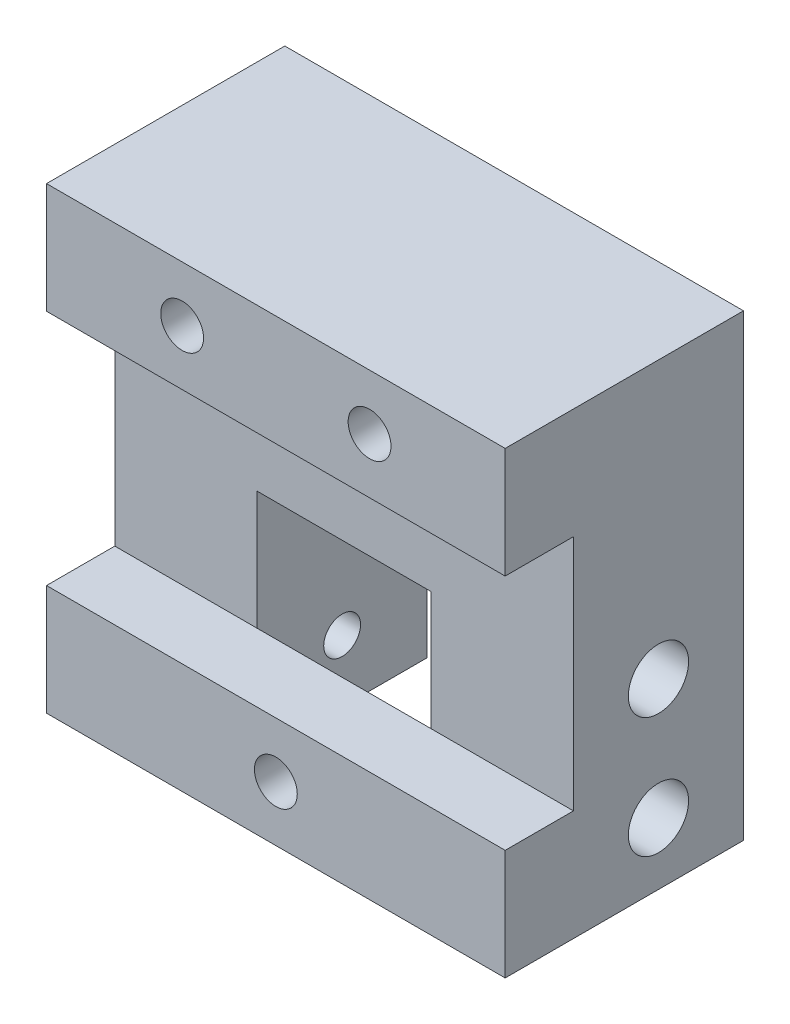
SolidWorks part; units mm, degrees
ref_plane "Front Plane" through (0, 0, 0) normal (0, 0, 1) x (1, 0, 0)
ref_plane "Top Plane" through (0, 0, 0) normal (0, 1, 0) x (1, 0, 0)
ref_plane "Right Plane" through (0, 0, 0) normal (1, 0, 0) x (0, 0, -1)
sketch "Sketch1" plane through (0, 0, 0) normal (0, 0, 1) x (1, 0, 0)
  line L1 (-34.26, 34.26) -> (34.26, 34.26)
  line L2 (-34.26, 34.26) -> (-34.26, -34.26)
  line L3 (-34.26, -34.26) -> (34.26, -34.26)
  line L4 (34.26, 34.26) -> (34.26, -34.26)
  point P4 (0, 34.26)
  point P6 (-34.26, 0)
  dimension "D1" = 68.52
extrude "Boss-Extrude1" add sketch "Sketch1" along normal blind 35.6
sketch "Sketch2" plane through (0, 0, 35.6) normal (0, 0, 1) x (1, 0, 0)
  line L0 (-34.26, 34.26) -> (-34.26, -34.26) construction
  line L1 (-34.26, -17.74) -> (34.26, -17.74)
  line L2 (-34.26, -17.74) -> (-34.26, 17.74)
  line L3 (-34.26, 17.74) -> (34.26, 17.74)
  line L4 (34.26, -17.74) -> (34.26, 17.74)
  line L5 (34.26, -34.26) -> (34.26, 34.26) construction
  point P8 (34.26, 0)
  dimension "D1" = 35.48
extrude "Cut-Extrude1" cut sketch "Sketch2" against normal blind 10.2
sketch "Sketch3" plane through (0, 0, 35.6) normal (0, 0, 1) x (1, 0, 0)
  line L0 (-14, 26) -> (14, 26) construction
  line L1 (0, -26) -> (0, 26) construction
  circle A0 centre (-14, 26) radius 3.2
  circle A1 centre (14, 26) radius 3.2
  circle A2 centre (0, -26) radius 3.2
  point P6 (0, 26)
  point P8 (0, 0)
  point P10 (-19.1017, 23.705)
  point P14 (0, 0)
  point P15 (0, 0)
  dimension "D2" = 6.4
  dimension "D3" = 6.4
  dimension "D4" = 6.4
  dimension "D1" = 52
  dimension "D5" = 28
extrude "Cut-Extrude2" cut sketch "Sketch3" against normal blind 10.2
sketch "Sketch4" plane through (0, 0, 0) normal (0, 0, -1) x (-1, 0, 0)
  line L0 (34.26, -34.26) -> (-34.26, -34.26) construction
  line L1 (-13, -34.26) -> (13, -34.26)
  line L2 (-13, -34.26) -> (-13, 0)
  line L3 (-13, 0) -> (13, 0)
  line L4 (13, -34.26) -> (13, 0)
  point P6 (0, 0)
  dimension "D1" = 26
extrude "Cut-Extrude3" cut sketch "Sketch4" against normal blind 25.4
sketch "Sketch6" plane through (34.26, 0, 0) normal (1, 0, 0) x (0, 0, -1)
  line L0 (-25.4, 0) -> (0, 0) construction
  line L1 (-25.4, 0) -> (0, 0) construction
  circle A0 centre (-12.7, -7) radius 2.75
  circle A1 centre (-12.7, -25) radius 2.75
  point P2 (-12.7, -25.0074)
  point P5 (0, 0)
  point P7 (-12.7, 0)
  dimension "D2" = 5.5
  dimension "D3" = 5.5
  dimension "D1" = 7
  dimension "D4" = 25
extrude "Cut-Extrude4" cut sketch "Sketch6" against normal through all both and the other way through all
sketch "Sketch7" plane through (34.26, 0, 0) normal (1, 0, 0) x (0, 0, -1)
  circle A0 centre (-12.7, -7) radius 2.75 construction
  circle A1 centre (-12.7, -7) radius 2.75 construction
  circle A2 centre (-12.7, -7) radius 4.5
  circle A3 centre (-12.7, -25) radius 4.5
  dimension "D1" = 9
  dimension "D2" = 9
extrude "Cut-Extrude5" cut sketch "Sketch7" against normal offset from surface (13.26 mm away) 8 up to face at (13, -4.25, 12.7)
sketch "Sketch8" plane through (-34.26, 0, 0) normal (-1, 0, 0) x (0, 0, 1)
  circle A0 centre (12.7, -7) radius 4.5
  circle A1 centre (12.7, -25) radius 4.5
  dimension "D1" = 9
  dimension "D2" = 9
extrude "Cut-Extrude6" cut sketch "Sketch8" against normal offset from surface (13.26 mm away) 8 up to face at (-13, -9.75, 12.7)
